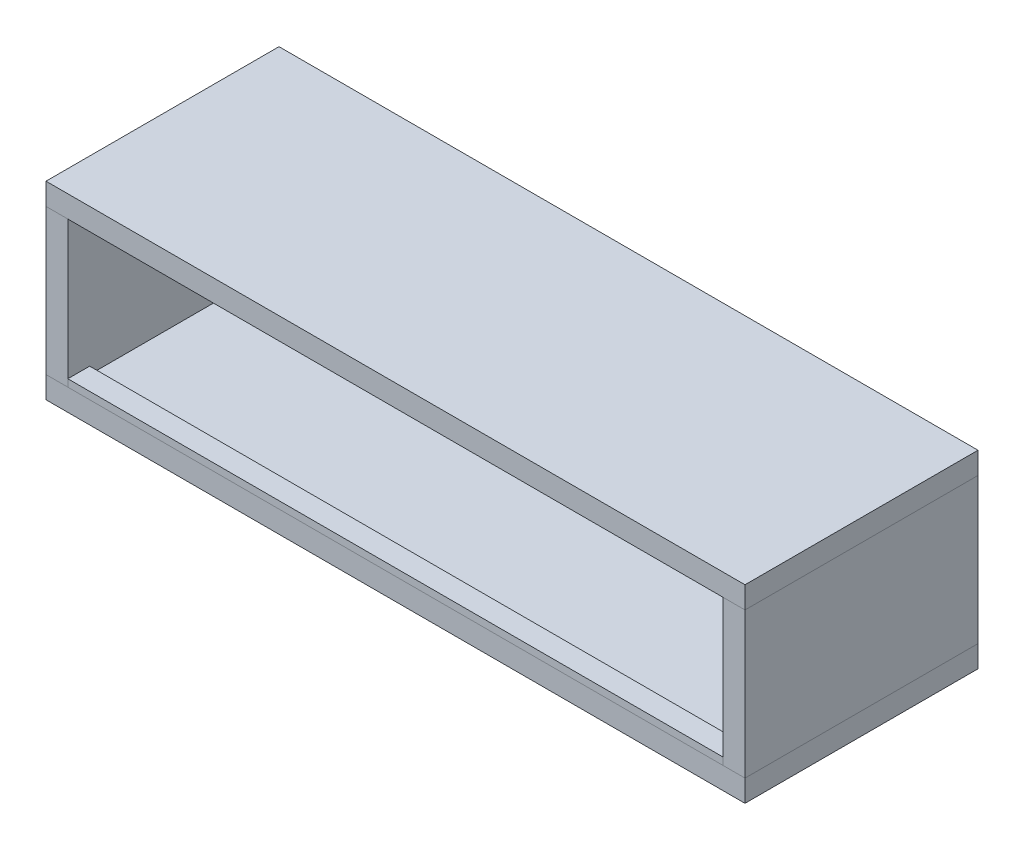
SolidWorks part; units mm, degrees
ref_plane "Front Plane" through (0, 0, 0) normal (0, 0, 1) x (1, 0, 0)
ref_plane "Top Plane" through (0, 0, 0) normal (0, 1, 0) x (1, 0, 0)
ref_plane "Right Plane" through (0, 0, 0) normal (1, 0, 0) x (0, 0, -1)
sketch "Sketch1" plane through (0, 0, 0) normal (0, 1, 0) x (1, 0, 0)
  line L1 (-304.8, 101.6) -> (304.8, 101.6)
  line L2 (-304.8, 101.6) -> (-304.8, -101.6)
  line L3 (-304.8, -101.6) -> (304.8, -101.6)
  line L4 (304.8, 101.6) -> (304.8, -101.6)
  line L5 (-304.8, 101.6) -> (304.8, -101.6) construction
  line L6 (-304.8, -101.6) -> (304.8, 101.6) construction
  point P0 (0, 0)
  dimension "D1" = 609.6
  dimension "D2" = 203.2
extrude "Boss-Extrude1" add sketch "Sketch1" along normal blind 19.05
sketch "Sketch2" plane through (0, 19.05, 0) normal (0, 1, 0) x (1, 0, 0)
  line L0 (-304.8, -101.6) -> (304.8, -101.6) construction
  line L1 (-304.8, 101.6) -> (-285.75, 101.6)
  line L2 (-304.8, 101.6) -> (-304.8, -101.6)
  line L3 (-304.8, -101.6) -> (-285.75, -101.6)
  line L4 (-285.75, 101.6) -> (-285.75, -101.6)
  line L5 (304.8, 101.6) -> (-304.8, 101.6) construction
  line L6 (304.8, -101.6) -> (285.75, -101.6)
  line L7 (304.8, -101.6) -> (304.8, 101.6)
  line L8 (304.8, 101.6) -> (285.75, 101.6)
  line L9 (285.75, -101.6) -> (285.75, 101.6)
  line L11 (-285.75, 101.6) -> (285.75, 101.6)
  line L12 (-285.75, 101.6) -> (-285.75, 82.55)
  line L13 (-285.75, 82.55) -> (285.75, 82.55)
  line L14 (285.75, 101.6) -> (285.75, 82.55)
  line M7 (304.8, -101.6) -> (304.8, 101.6)
  line M8 (304.8, 101.6) -> (-304.8, 101.6)
  line M9 (-304.8, 101.6) -> (-304.8, -101.6)
  line M10 (-304.8, -101.6) -> (304.8, -101.6)
  dimension "D1" = 19.05
  dimension "D2" = 19.05
  dimension "D3" = 19.05
extrude "Boss-Extrude2" add sketch "Sketch2" along normal blind 127 separate body contours L4 M8 M9 M10 | L9 M10 M7 M8 region at (-295.275, 19.05, 0) region at (295.275, 19.05, 0)
extrude "Boss-Extrude3" add sketch "Sketch2<3>" along normal up to surface (127 mm away) separate body contours L4 L13 L9 M8 region at (0, 19.05, -92.075) up to face at (-295.275, 146.05, 0)
sketch "Sketch2<3>" plane through (0, 19.05, 0) normal (0, 1, 0) x (1, 0, 0) same geometry as "Sketch2"
sketch "Sketch3" plane through (0, 146.05, 0) normal (0, 1, 0) x (1, 0, 0)
  line L1 (-304.8, 101.6) -> (304.8, 101.6)
  line L2 (-304.8, 101.6) -> (-304.8, -101.6)
  line L3 (-304.8, -101.6) -> (304.8, -101.6)
  line L4 (304.8, 101.6) -> (304.8, -101.6)
extrude "Boss-Extrude4" add sketch "Sketch3" along normal blind 19.05 separate body
sketch "Sketch4" plane through (0, 19.05, 0) normal (0, 1, 0) x (1, 0, 0)
  line L0 (285.75, -101.6) -> (285.75, 101.6) construction
  line L1 (-285.75, -101.6) -> (285.75, -101.6)
  line L2 (-285.75, -101.6) -> (-285.75, -82.55)
  line L3 (-285.75, -82.55) -> (285.75, -82.55)
  line L4 (285.75, -101.6) -> (285.75, -82.55)
  dimension "D1" = 19.05
extrude "Boss-Extrude5" add sketch "Sketch4" along normal blind 6.35 separate body
